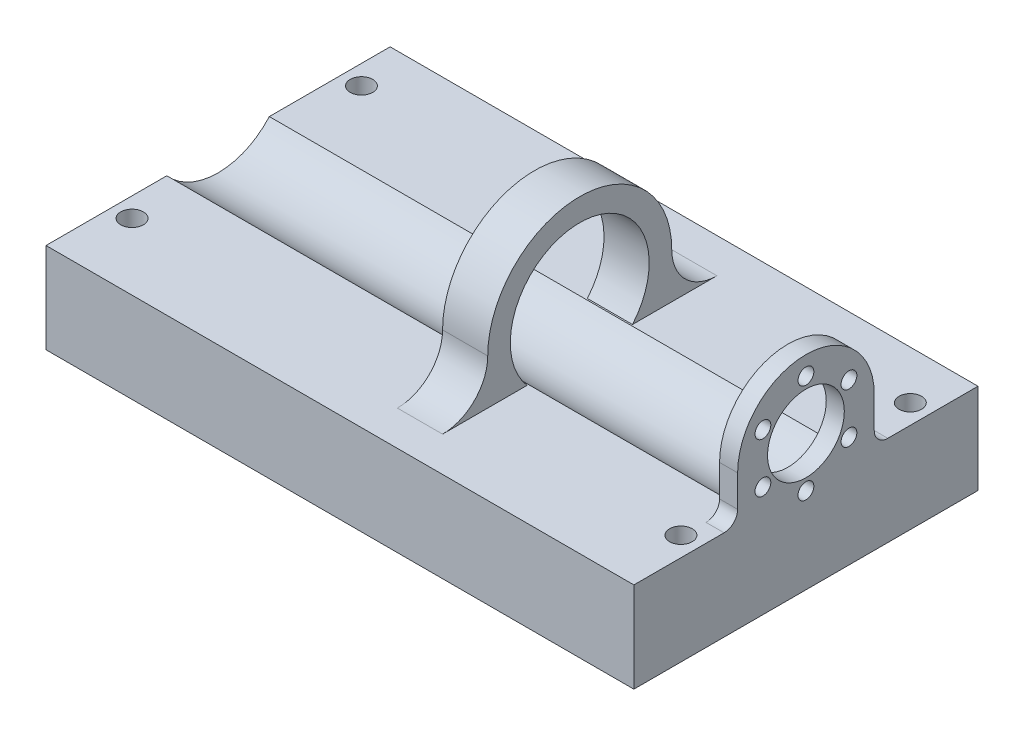
SolidWorks part; units mm, degrees
ref_plane "Front Plane" through (0, 0, 0) normal (0, 0, 1) x (1, 0, 0)
ref_plane "Top Plane" through (0, 0, 0) normal (0, 1, 0) x (1, 0, 0)
ref_plane "Right Plane" through (0, 0, 0) normal (1, 0, 0) x (0, 0, -1)
sketch "Sketch1" plane through (0, 0, 0) normal (0, 1, 0) x (1, 0, 0)
  line L1 (-65.0875, -38.1) -> (65.0875, -38.1)
  line L2 (-65.0875, -38.1) -> (-65.0875, 38.1)
  line L3 (-65.0875, 38.1) -> (65.0875, 38.1)
  line L4 (65.0875, -38.1) -> (65.0875, 38.1)
  line L5 (-65.0875, -38.1) -> (65.0875, 38.1) construction
  line L6 (-65.0875, 38.1) -> (65.0875, -38.1) construction
  point P0 (0, 0)
  dimension "D1" = 130.175
  dimension "D2" = 76.2
extrude "Boss-Extrude1" add sketch "Sketch1" along normal blind 20
sketch "Sketch2" plane through (65.0875, 0, 0) normal (1, 0, 0) x (0, 0, -1)
  line L3 (-38.1, 20) -> (38.1, 20) construction
  circle A0 centre (0, 30) radius 15.125
  point P6 (0, 20)
  dimension "D1" = 30.25
  dimension "D2" = 10
extrude "Cut-Extrude1" cut sketch "Sketch2" against normal through all
sketch "Sketch3" plane through (65.0875, 0, 0) normal (1, 0, 0) x (0, 0, -1)
  circle A0 centre (0, 30) radius 15.125
extrude "Boss-Extrude2" add sketch "Sketch3" against normal blind 4
ref_axis "Axis1" through (-65.0875, 30, 0) along (1, 0, 0)
sketch "Sketch4" plane through (61.0875, 0, 0) normal (-1, 0, 0) x (0, 0, 1)
  circle A1 centre (0, 41) radius 1.75
  dimension "D2" = 3.5
  dimension "D1" = 11
extrude "Cut-Extrude2" cut sketch "Sketch4" against normal through all
pattern_circular "CirPattern1" count 6 over 360 about axis through (-65.0875, 30, 0) along (1, 0, 0) of "Cut-Extrude2"
sketch "Sketch5" plane through (65.0875, 0, 0) normal (1, 0, 0) x (0, 0, -1)
  circle A0 centre (0, 30) radius 8.5
  dimension "D1" = 17
extrude "Cut-Extrude3" cut sketch "Sketch5" against normal through all
sketch "Sketch6" plane through (0, 0, 0) normal (0, -1, 0) x (1, 0, 0)
  line L0 (65.0875, 38.1) -> (65.0875, -38.1) construction
  line L3 (60.7695, 25.868) -> (65.0875, 25.868) construction
  line L4 (-65.0875, 38.1) -> (65.0875, 38.1) construction
  line L5 (60.7695, -24.932) -> (65.0875, -24.932) construction
  circle A0 centre (60.7695, 23.368) radius 2.5
  circle A1 centre (60.7695, -27.432) radius 2.5
  dimension "D1" = 5
  dimension "D2" = 4.318
  dimension "D3" = 14.732
  dimension "D4" = 50.8
extrude "Cut-Extrude4" cut sketch "Sketch6" against normal through all
mirror "Mirror1" about plane through (0, 0, 0) normal (1, 0, 0) of "Cut-Extrude4"
ref_plane "Plane1" through (10, 0, 0) normal (1, 0, 0) x (0, 0, -1)
sketch "Sketch8" plane through (10, 0, 0) normal (1, 0, 0) x (0, 0, -1)
  line L0 (-11.3475, 20) -> (-17.7522, 20)
  line L1 (-38.1, 20) -> (-11.3475, 20) construction
  line L2 (11.3475, 20) -> (17.7522, 20)
  arc A0 (11.3475, 20) -> (-11.3475, 20) centre (0, 30) ccw construction
  arc A1 (11.3475, 20) -> (-11.3475, 20) centre (0, 30) ccw
  circle A2 centre (0, 30) radius 20.375
  circle A3 centre (0, 30) radius 15.375
  dimension "D1" = 0.25
  dimension "D2" = 5
extrude "Boss-Extrude3" add sketch "Sketch8" along normal mid plane 10 contours L2 A2 L0 A1 region at (10, 20.5083, 14.7154)
sketch "Sketch9" plane through (65.0875, 0, 0) normal (1, 0, 0) x (0, 0, -1)
  line L0 (-15.125, 30) -> (-15.125, 20)
  line L3 (-38.1, 20) -> (-11.3475, 20) construction
  line L4 (15.125, 30) -> (15.125, 20)
  line L6 (11.3475, 20) -> (38.1, 20) construction
  line L7 (15.125, 20) -> (11.3475, 20)
  line L8 (-15.125, 20) -> (-11.3475, 20)
  arc A1 (11.3475, 20) -> (-11.3475, 20) centre (0, 30) ccw construction
  arc A3 (11.3475, 20) -> (-11.3475, 20) centre (0, 30) ccw
  line M9 (38.1, 20) -> (11.3475, 20)
  arc M10 (11.3475, 20) -> (-11.3475, 20) centre (0, 30) ccw
  line M11 (-11.3475, 20) -> (-38.1, 20)
extrude "Boss-Extrude4" add sketch "Sketch9" against normal up to surface (4 mm away) contours L0 M10 M11 | L4 M10 M9 region at (65.0875, 22.4333, 14.021) region at (65.0875, 22.4333, -14.021) up to face at (61.0875, 30, -8.5)
sketch "Sketch10" plane through (10, 0, 0) normal (1, 0, 0) x (0, 0, -1)
  line L0 (17.7522, 20) -> (50017.7522, 20) construction
  line L1 (20.375, 30) -> (20.375, 20)
  line L2 (20.375, 20) -> (17.7522, 20)
  line L3 (-20.375, 30) -> (-20.375, 20)
  line L4 (-20.375, 20) -> (-17.7522, 20)
  arc A0 (17.7522, 20) -> (-17.7522, 20) centre (0, 30) ccw construction
  arc A1 (17.7522, 20) -> (-17.7522, 20) centre (0, 30) ccw
extrude "Boss-Extrude5" add sketch "Sketch10" against normal up to surface (5 mm away) and the other way up to surface (5 mm away) contours A1 L3 L4 | A1 L2 L1 region at (10, 22.4667, -19.5977) region at (10, 22.4667, 19.5977) up to face at (5, 33.9375, 0) other way up to face at (15, 33.9375, 0)
fillet "Fillet1" radius 10 2 edges at (10, 20, -20.375) (10, 20, 20.375)
fillet "Fillet2" radius 3 2 edges at (63.0875, 20, -15.125) (63.0875, 20, 15.125)
